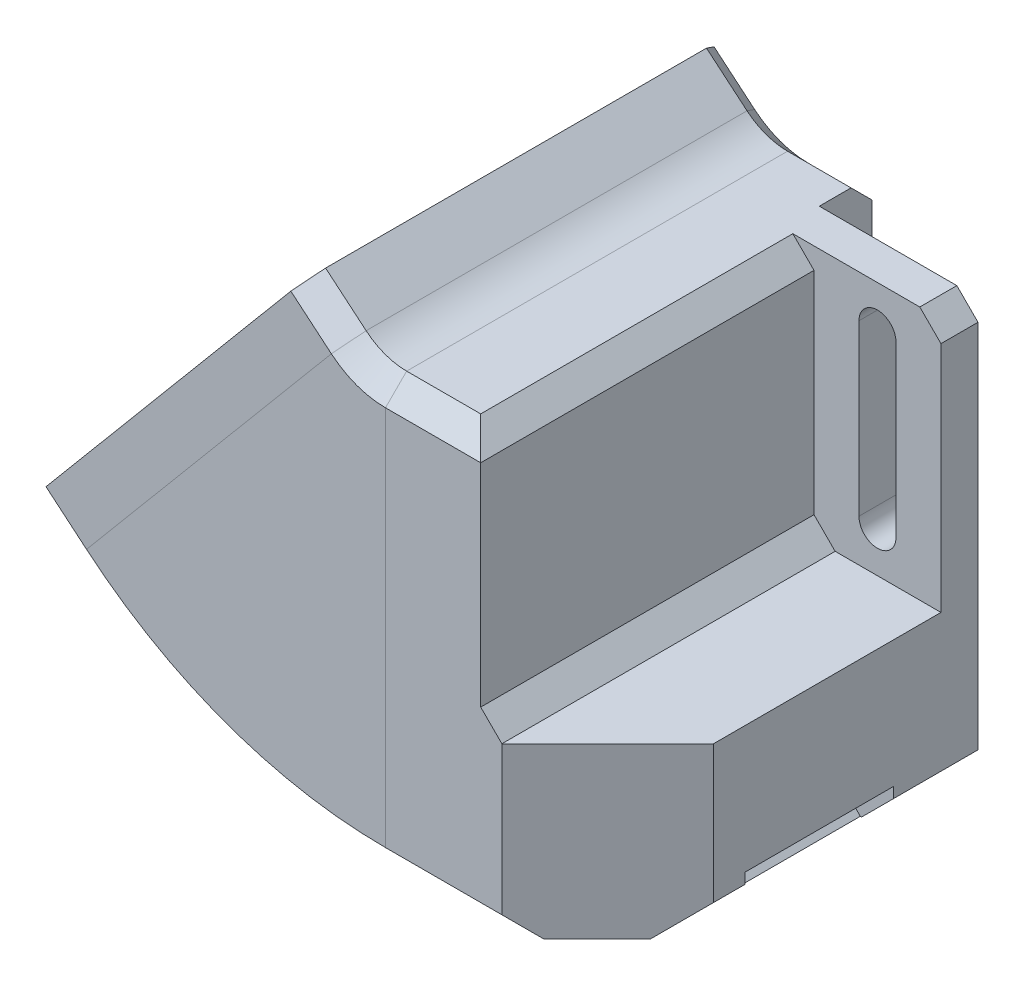
SolidWorks part; units mm, degrees
ref_plane "Front Plane" through (0, 0, 0) normal (0, 0, 1) x (1, 0, 0)
ref_plane "Top Plane" through (0, 0, 0) normal (0, 1, 0) x (1, 0, 0)
ref_plane "Right Plane" through (0, 0, 0) normal (1, 0, 0) x (0, 0, -1)
sketch "Sketch2" plane through (0, 0, 0) normal (0, 0, 1) x (1, 0, 0)
  line L0 (0, 0) -> (-5, 0)
  line L1 (-34.5417, 10.7523) -> (-38.3719, 13.9662)
  line L2 (-38.3719, 13.9662) -> (-12.6604, 44.608) construction
  line L3 (-12.6604, 44.608) -> (-5, 38.1801) construction
  line L4 (-5, 38.1801) -> (0, 38.1801) construction
  line L5 (0, 38.1801) -> (0, 0) construction
  arc A0 (-5, 0) -> (-34.5417, 10.7523) centre (-5, 45.9588) cw
  dimension "D1" = 5
  dimension "D2" = 5
  dimension "D3" = 40
  dimension "D4" = 40
  dimension "D5" = 10
sketch "Sketch3" plane through (0, 0, 0) normal (1, 0, 0) x (0, 0, -1)
  line L0 (-17, 37) -> (17, 3) construction
  line L1 (-20, 0) -> (20, 0)
  line L2 (-20, 0) -> (-20, 40)
  line L3 (-20, 40) -> (20, 40)
  line L4 (20, 0) -> (20, 40)
  line L5 (-17, 3) -> (17, 3)
  line L6 (-17, 3) -> (-17, 37)
  line L7 (-17, 37) -> (17, 37)
  line L8 (17, 3) -> (17, 37)
  line L10 (-20, 0) -> (20, 40) construction
  point P8 (0, 20)
  dimension "D1" = 40
  dimension "D2" = 34
sweep "Sweep1" add profiles "Sketch3" path "Sketch2"
sketch "Sketch4" plane through (0, 0, 0) normal (0, 1, 0) x (1, 0, 0)
  line L0 (0, 20) -> (10.583, 8)
  line L1 (10.583, -8) -> (0, -20)
  line L2 (0, -20) -> (0, 20)
  line L3 (10.583, 8) -> (10.583, -8)
  line L4 (10.583, 0) -> (0, 0) construction
  dimension "D1" = 16
  dimension "D2" = 16
sketch "Sketch5" plane through (0, 0, 0) normal (1, 0, 0) x (0, 0, -1)
  line L0 (20, 0) -> (20, 40) construction
  line L1 (-20, 0) -> (20, 0)
  line L2 (-20, 0) -> (-20, 20)
  line L3 (-20, 20) -> (20, 20)
  line L4 (20, 0) -> (20, 20)
  line L5 (17, 37) -> (17, 3) construction
  line L6 (-17, 3) -> (17, 3)
  line L7 (-17, 3) -> (-17, 18)
  line L8 (-17, 18) -> (17, 18)
  line L9 (17, 3) -> (17, 18)
  dimension "D1" = 2
sketch "Sketch7" plane through (0, 0, 0) normal (0, 1, 0) x (1, 0, 0)
  line L1 (0, -20) -> (16, -20)
  line L2 (0, -20) -> (0, 8)
  line L3 (0, 8) -> (16, 8)
  line L4 (16, -20) -> (16, 8)
  dimension "D1" = 8
  dimension "D2" = 16
extrude "Boss-Extrude2" add sketch "Sketch7" along normal up to surface (40 mm away) up to face at (-2.5, 40, 0)
sketch "Sketch8" plane through (0, 0, 0) normal (1, 0, 0) x (0, 0, -1)
  line L1 (20, 0) -> (7, 0)
  line L2 (20, 0) -> (20, 40)
  line L3 (20, 40) -> (7, 40)
  line L4 (7, 0) -> (7, 40)
  dimension "D1" = 13
extrude "Boss-Extrude5" add sketch "Sketch8" against normal blind 5 and the other way blind 1
chamfer "Chamfer1" distance 6 angle 45 1 edges at (-5, 20, -17)
chamfer "Chamfer2" distance 4 angle 45 1 edges at (-5, 20, -7)
sketch "Sketch9" plane through (16, 0, 0) normal (1, 0, 0) x (0, 0, -1)
  line L0 (-20, 0) -> (8, 0) construction
  line L1 (7, 1) -> (-7, 1)
  line L2 (7, 1) -> (7, 4)
  line L3 (7, 4) -> (-7, 4)
  line L4 (-7, 1) -> (-7, 4)
  line L5 (8, 40) -> (8, 0) construction
  line L6 (0, 0) -> (0, 1) construction
  dimension "D1" = 1
  dimension "D2" = 4
  dimension "D3" = 1
extrude "Cut-Extrude1" cut sketch "Sketch9" against normal up to surface (16 mm away) up to face at (0, 20, 5)
sketch "Sketch10" plane through (0, 0, 20) normal (0, 0, 1) x (1, 0, 0)
  line L0 (16, 0) -> (-5, 0) construction
  line L1 (16, 40) -> (4, 40)
  line L2 (16, 40) -> (16, 16)
  line L3 (16, 16) -> (4, 16)
  line L4 (4, 40) -> (4, 16)
  dimension "D1" = 12
  dimension "D2" = 16
extrude "Cut-Extrude2" cut sketch "Sketch10" against normal through all
sketch "Sketch11" plane through (0, 0, -8) normal (0, 0, -1) x (-1, 0, 0)
  line L1 (-1, 40) -> (-16, 40)
  line L2 (-1, 40) -> (-1, 0)
  line L3 (-1, 0) -> (-16, 0)
  line L4 (-16, 40) -> (-16, 0)
extrude "Boss-Extrude6" add sketch "Sketch11" along normal blind 7
sketch "Sketch12" plane through (0, 0, -8) normal (0, 0, 1) x (1, 0, 0)
  line L1 (10, 36) -> (10, 20) construction
  line L2 (11.75, 36) -> (11.75, 20)
  line L3 (8.25, 36) -> (8.25, 20)
  line L4 (16, 40) -> (16, 16) construction
  line L5 (4, 40) -> (16, 40) construction
  line L6 (4, 16) -> (16, 16) construction
  arc A0 (11.75, 36) -> (8.25, 36) centre (10, 36) ccw
  arc A1 (8.25, 20) -> (11.75, 20) centre (10, 20) ccw
  point P2 (10, 28)
  dimension "D1" = 6
  dimension "D2" = 3.5
  dimension "D3" = 4
  dimension "D4" = 4
extrude "Cut-Extrude3" cut sketch "Sketch12" against normal through all
sketch "Sketch13" plane through (0, 40, 0) normal (0, 1, 0) x (1, 0, 0)
  line L0 (16, 15) -> (16, 8) construction
  line L1 (4, 8) -> (16, 8)
  line L2 (4, 8) -> (4, 11.5)
  line L3 (4, 11.5) -> (16, 11.5)
  line L4 (16, 8) -> (16, 11.5)
extrude "Cut-Extrude4" cut sketch "Sketch13" against normal up to surface (24 mm away) up to face at (10, 16, 6)
sketch "Sketch15" plane through (-29.3946, 24.665, 0) normal (-0.766, 0.6428, 0) x (0, 0, 1)
  line L1 (-17, 23.0338) -> (-12.5, 23.0338)
  line L2 (-17, 23.0338) -> (-17, 18.5338)
  line L3 (-17, 18.5338) -> (-12.5, 18.5338)
  line L4 (-12.5, 23.0338) -> (-12.5, 18.5338)
  line L5 (17, 23.0338) -> (12.5, 23.0338)
  line L6 (17, 23.0338) -> (17, 18.5338)
  line L7 (17, 18.5338) -> (12.5, 18.5338)
  line L8 (12.5, 23.0338) -> (12.5, 18.5338)
  line L9 (-17, -10.9662) -> (-12.5, -10.9662)
  line L10 (-17, -10.9662) -> (-17, -6.4662)
  line L11 (-17, -6.4662) -> (-12.5, -6.4662)
  line L12 (-12.5, -10.9662) -> (-12.5, -6.4662)
  line L13 (17, -10.9662) -> (12.5, -10.9662)
  line L14 (17, -10.9662) -> (17, -6.4662)
  line L15 (17, -6.4662) -> (12.5, -6.4662)
  line L16 (12.5, -10.9662) -> (12.5, -6.4662)
  dimension "D1" = 4.5
extrude "Boss-Extrude7" add sketch "Sketch15" against normal blind 5
sketch "Sketch14" plane through (-29.3946, 24.665, 0) normal (-0.766, 0.6428, 0) x (0, 0, 1)
  line L0 (-16, -9.9662) -> (16, 22.0338) construction
  line L1 (-16, 22.0338) -> (16, 22.0338) construction
  line L2 (-16, 22.0338) -> (-16, -9.9662) construction
  line L3 (-16, -9.9662) -> (16, -9.9662) construction
  line L4 (16, 22.0338) -> (16, -9.9662) construction
  line L5 (-20, 26.0338) -> (20, -13.9662) construction
  circle A0 centre (-16, 22.0338) radius 1.5
  circle A1 centre (16, 22.0338) radius 1.5
  circle A2 centre (-16, -9.9662) radius 1.5
  circle A3 centre (16, -9.9662) radius 1.5
  point P10 (0, 6.0338)
  dimension "D1" = 3
  dimension "D2" = 32
extrude "Cut-Extrude5" cut sketch "Sketch14" against normal blind 8
chamfer "Chamfer3" distance 14 angle 45 1 edges at (0, 4, 0)
chamfer "Chamfer7" distance 3 angle 45 1 edges at (16, 0, 2.5)
chamfer "Chamfer4" distance 14 angle 45 1 edges at (0, 10.5, 7)
chamfer "Chamfer5" distance 2 angle 45 1 edges at (0, 3, 0)
chamfer "Chamfer9" distance 2 angle 45 3 edges at (4, 40, 4.25) (4, 16, 4.25) (16, 40, -13.25)
chamfer "Chamfer10" distance 1.5 angle 90 1 edges at (14, 1, 0) first distance on face at (14.75, 1.75, 1.25)
chamfer "Chamfer11" distance 10 angle 45 1 edges at (16, 9.5, 20)
chamfer "Chamfer12" distance 2 angle 45 16 edges at (-10.7453, 43.0011, -20) (-7.038, 40.3594, -20) (-2, 40, -20) (-36.4568, 12.3593, -20) (-20.7188, 2.7717, -20) (-2, 0, -20) (-36.4568, 12.3593, 20) (-20.7188, 2.7717, 20) (0.5, 0, 20) (-10.7453, 43.0011, 20) (-7.038, 40.3594, 20) (-1.5, 40, 20) (-31.6359, 18.1046, 12.5) (-15.5662, 37.2557, 12.5) (-15.5662, 37.2557, -12.5) (-31.6359, 18.1046, -12.5)
